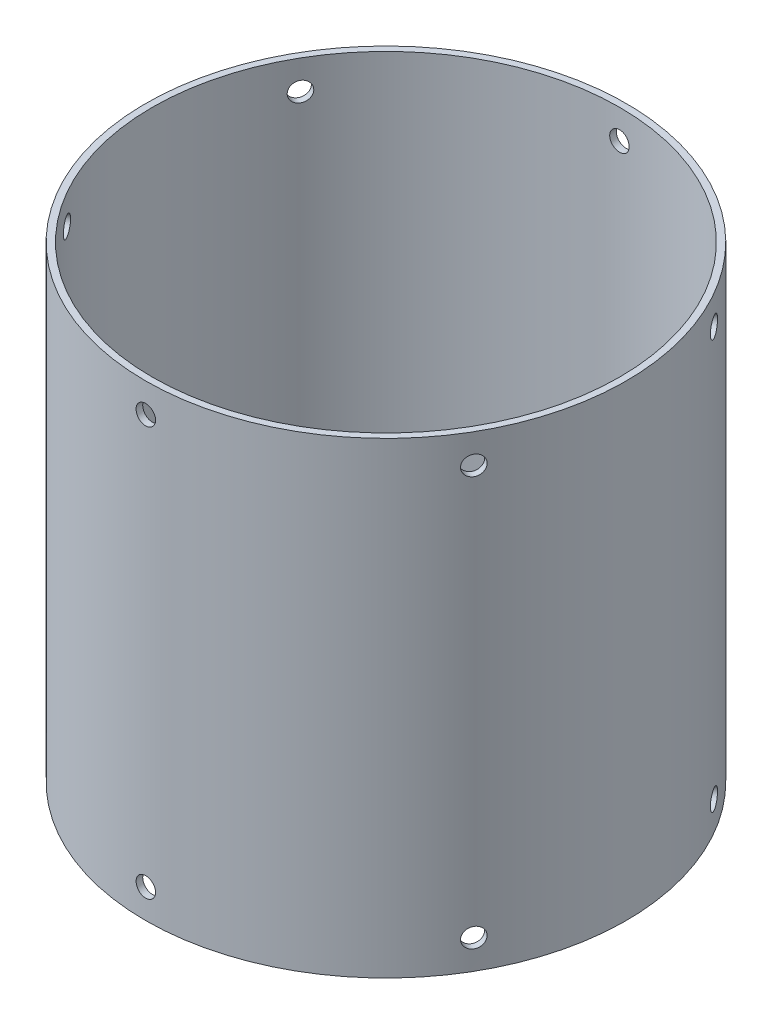
SolidWorks part; units mm, degrees
material "Acrylic (Medium-high impact)"
ref_plane "Front Plane" through (0, 0, 0) normal (0, 0, 1) x (1, 0, 0)
ref_plane "Top Plane" through (0, 0, 0) normal (0, 1, 0) x (1, 0, 0)
ref_plane "Right Plane" through (0, 0, 0) normal (1, 0, 0) x (0, 0, -1)
sketch "Sketch1" plane through (0, 0, 0) normal (0, 1, 0) x (1, 0, 0)
  circle A0 centre (0, 0) radius 76.2
  circle A1 centre (0, 0) radius 78.359
  dimension "D1" = 152.4
  dimension "D2" = 156.718
extrude "Boss-Extrude1" add sketch "Sketch1" along normal blind 152.4
sketch "Sketch2" plane through (0, 0, 0) normal (0, 0, 1) x (1, 0, 0)
  line L0 (0, 0) -> (0, 234.7266) construction
  line L1 (-76.2, 0) -> (76.2, 0) construction
  line L2 (-78.359, 0) -> (78.359, 0) construction
  line L3 (78.359, 76.2) -> (-54.7898, 76.2) construction
  line L4 (78.359, 0) -> (78.359, 152.4) construction
  circle A0 centre (0, 9.525) radius 3.175
  circle A1 centre (0, 142.875) radius 3.175
  dimension "D1" = 9.525
extrude "Cut-Extrude1" cut sketch "Sketch2" against normal through all
ref_axis "Axis1" through (0, 0, 0) along (0, 1, 0)
pattern_circular "CirPattern1" count 6 over 360 about axis through (0, 0, 0) along (0, 1, 0) of "Cut-Extrude1"
